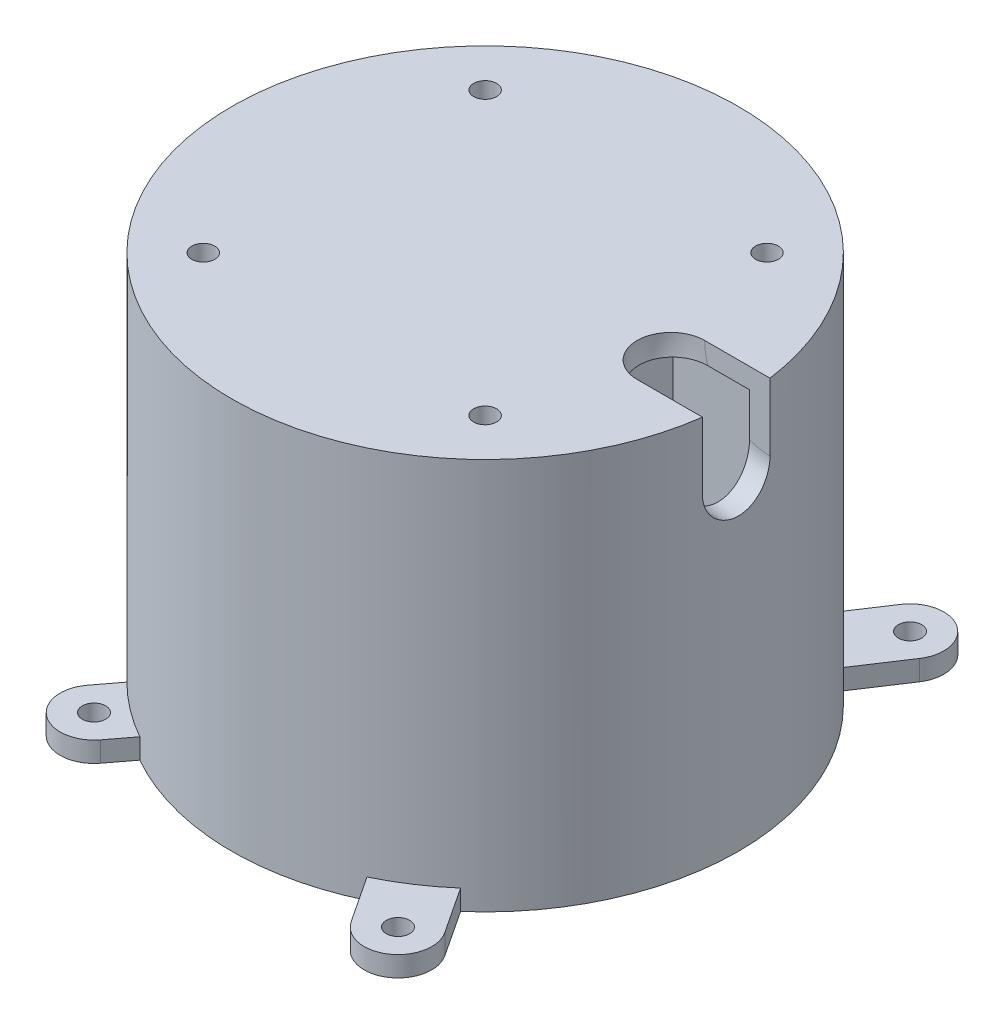
SolidWorks part; units mm, degrees
ref_plane "Front Plane" through (0, 0, 0) normal (0, 0, 1) x (1, 0, 0)
ref_plane "Top Plane" through (0, 0, 0) normal (0, 1, 0) x (1, 0, 0)
ref_plane "Right Plane" through (0, 0, 0) normal (1, 0, 0) x (0, 0, -1)
sketch "Sketch1" plane through (0, 0, 0) normal (0, 1, 0) x (1, 0, 0)
  circle A6 centre (0, 0) radius 37.5
  dimension "D1" = 75
extrude "Boss-Extrude2" add sketch "Sketch1" against normal blind 3
sketch "Sketch2" plane through (0, -3, 0) normal (0, -1, 0) x (1, 0, 0)
  line L4 (0, 32.7824) -> (0, 0) construction
  circle A0 centre (0, 0) radius 34.5
  circle A1 centre (0, 0) radius 37.5
  circle A2 centre (0, 0) radius 37.5
  point P5 (0, 34.025)
  point P7 (10.4973, 36.0008)
  point P8 (10.4066, 32.7824)
  dimension "D2" = 3
  dimension "D1" = 0
extrude "Boss-Extrude3" add sketch "Sketch2" along normal blind 55
sketch "Sketch3" plane through (0, -3, 0) normal (0, -1, 0) x (1, 0, 0)
  line L0 (13.5, 34.9857) -> (13.5, 31.749)
  line L8 (13.5, 31.749) -> (-13.5, 31.749)
  line L9 (-13.5, 31.749) -> (-13.5, 34.9857)
  line L10 (0, 0) -> (-12.0832, 0) construction
  line L11 (-13.5, -31.749) -> (-13.5, -34.9857)
  line L12 (13.5, -31.749) -> (-13.5, -31.749)
  line L13 (13.5, -34.9857) -> (13.5, -31.749)
  circle A4 centre (0, 0) radius 37.5 construction
  arc A5 (13.5, 34.9857) -> (-13.5, 34.9857) centre (0, 0) ccw
  circle A6 centre (0, 0) radius 34.5 construction
  arc A7 (13.5, -34.9857) -> (-13.5, -34.9857) centre (0, 0) cw
  dimension "D1" = 27
extrude "Boss-Extrude4" add sketch "Sketch3" along normal up to surface (55 mm away) up to face at (0, -58, -37.5)
sketch "Sketch4" plane through (0, 0, 0) normal (0, 0, 1) x (1, 0, 0)
  line L0 (-12.625, -14.83) -> (-12.625, -9.67) construction
  line L1 (12.625, -9.67) -> (12.625, -14.83) construction
  line L2 (-12.625, -14.83) -> (-12.625, -9.67) construction
  line L3 (12.625, -9.67) -> (12.625, -14.83) construction
  line L4 (-12.825, -3) -> (-12.825, -14.83)
  line L5 (-12.125, -17.0499) -> (-12.125, -19.0499)
  line L6 (-12.125, -19.0499) -> (-17.825, -19.0499)
  line L7 (-17.825, -19.0499) -> (-17.825, -3)
  line L8 (-17.825, -3) -> (-12.825, -3)
  line L10 (0, 0) -> (0, -13.0317) construction
  line L11 (17.825, -19.0499) -> (17.825, -3)
  line L12 (12.125, -19.0499) -> (17.825, -19.0499)
  line L13 (12.125, -17.0499) -> (12.125, -19.0499)
  line L14 (12.825, -3) -> (12.825, -14.83)
  line L15 (17.825, -3) -> (12.825, -3)
  line L16 (13.5, -3) -> (34.5, -3) construction
  arc A0 (-12.825, -14.83) -> (-12.125, -17.0499) centre (-8.955, -14.83) ccw
  arc A2 (12.825, -14.83) -> (12.125, -17.0499) centre (8.955, -14.83) cw
  arc A3 (-12.625, -14.83) -> (-8.955, -18.5) centre (-8.955, -14.83) ccw construction
  point P12 (0, 0)
  point P27 (-12.1309, -18.4005)
  dimension "D1" = 0.2
  dimension "D2" = 0.7
  dimension "D3" = 2
  dimension "D4" = 5
extrude "Boss-Extrude5" add sketch "Sketch4" along normal mid plane 20
ref_plane "Plane1" through (37.5, 0, 0) normal (1, 0, 0) x (0, 0, -1)
sketch "Sketch7" plane through (0, -58, 0) normal (0, -1, 0) x (1, 0, 0)
  circle A0 centre (0, 0) radius 37.5
  circle A1 centre (0, 0) radius 31.5
  circle A2 centre (0, 0) radius 37.5 construction
  dimension "D1" = 6
extrude "Boss-Extrude7" add sketch "Sketch7" against normal blind 3
hole_wizard "M3 Clearance Hole1" positions "Sketch8" profile "Sketch10" hole size "M3" standard "ANSI Metric" end condition through all
sketch "Sketch8" plane through (0, -3, 0) normal (0, -1, 0) x (-1, 0, 0)
  circle A2 centre (20.8597, -20.8597) radius 1.6
  circle A3 centre (20.8597, -20.8597) radius 1.6
  circle A6 centre (-20.8597, -20.8597) radius 1.6
  circle A7 centre (-20.8597, -20.8597) radius 1.6
  circle A10 centre (-20.8597, 20.8597) radius 1.6
  circle A11 centre (-20.8597, 20.8597) radius 1.6
  circle A14 centre (20.8597, 20.8597) radius 1.6
  circle A15 centre (20.8597, 20.8597) radius 1.6
  point P5 (20.8597, -20.8597)
  point P12 (-20.8597, -20.8597)
  point P19 (-20.8597, 20.8597)
  point P26 (20.8597, 20.8597)
  dimension "D1" = 0
  dimension "D2" = 0
  dimension "D3" = 0
  dimension "D4" = 0
sketch "Sketch10" plane through (-20.8597, -3, 20.8597) normal (1, 0, 0) x (0, 0, -1)
  line L0 (0, 0) -> (0, 3)
  line L1 (0, 3) -> (1.7, 3)
  line L2 (1.7, 3) -> (1.7, 0)
  line L5 (1.7, 0) -> (0, 0)
  line L11 (0, -6.35) -> (0, 107.95) construction
  dimension "Thru Hole Dia." = 3.4
  dimension "Thru Hole Depth" = 3
sketch "Sketch11" plane through (0, 0, 0) normal (0, 1, 0) x (1, 0, 0)
  line L0 (37.5, -5) -> (27.5, -5)
  line L1 (27.5, 5) -> (37.5, 5)
  line L2 (27.5, 0) -> (0, 0) construction
  line L3 (37.5, -5) -> (37.5, 5)
  arc A0 (27.5, -5) -> (27.5, 5) centre (27.5, 0) cw
  circle A1 centre (0, 0) radius 37.5 construction
  point P2 (22.5, 0)
  point P3 (0, 0)
  point P4 (37.5, 0)
  point P9 (36.8473, 1.8668)
  point P12 (0, 0)
  dimension "D3" = 15
  dimension "D2" = 10
revolve "Cut-Revolve1" cut sketch "Sketch11" angle 360 about L3
sketch "Sketch14" plane through (0, -58, 0) normal (0, -1, 0) x (1, 0, 0)
  line L0 (25, 37.9) -> (25, 32.9)
  line L1 (25, 32.9) -> (-25, 32.9)
  line L2 (0, -32.9) -> (0, 32.9)
  line L3 (0, 0) -> (13.3551, 0) construction
  line L4 (25, -32.9) -> (-25, -32.9)
  line L5 (25, -37.9) -> (25, -32.9)
  point P7 (0, 0)
  dimension "D1" = 50
  dimension "D2" = 5
  dimension "D3" = 65.8
sketch "Sketch15" plane through (0, -58, 0) normal (0, -1, 0) x (1, 0, 0)
  line L0 (24.6379, 28.2705) -> (29.1738, 35.1469)
  line L1 (20.8262, 40.6531) -> (16.2904, 33.7768)
  line L2 (-26.4668, 26.5661) -> (-28.981, 29.8749)
  line L3 (-21.019, 35.9251) -> (-18.5047, 32.6163)
  line L5 (-25, 32.9) -> (0, 0) construction
  line L6 (0, 0) -> (25, 37.9) construction
  line L7 (0, 0) -> (-26.4668, 0) construction
  line L8 (-21.019, -35.9251) -> (-18.5047, -32.6163)
  line L9 (-26.4668, -26.5661) -> (-28.981, -29.8749)
  line L10 (24.6379, -28.2705) -> (29.1738, -35.1469)
  line L11 (20.8262, -40.6531) -> (16.2904, -33.7768)
  circle A0 centre (0, 0) radius 37.5 construction
  arc A1 (29.1738, 35.1469) -> (20.8262, 40.6531) centre (25, 37.9) ccw
  arc A2 (-18.5047, 32.6163) -> (-26.4668, 26.5661) centre (0, 0) ccw
  arc A3 (-28.981, 29.8749) -> (-21.019, 35.9251) centre (-25, 32.9) cw
  arc A4 (24.6379, 28.2705) -> (16.2904, 33.7768) centre (0, 0) ccw
  arc A5 (-28.981, -29.8749) -> (-21.019, -35.9251) centre (-25, -32.9) ccw
  arc A6 (-18.5047, -32.6163) -> (-26.4668, -26.5661) centre (0, 0) cw
  arc A7 (29.1738, -35.1469) -> (20.8262, -40.6531) centre (25, -37.9) cw
  arc A8 (24.6379, -28.2705) -> (16.2904, -33.7768) centre (0, 0) cw
  dimension "D1" = 10
extrude "Boss-Extrude8" add sketch "Sketch15" against normal blind 3
hole_wizard "Tap Drill for #8-32 Tap1" positions "Sketch16" profile "Sketch17" hole size "#8-32" standard "ANSI Inch" end condition through all
sketch "Sketch16" plane through (0, -58, 0) normal (0, -1, 0) x (-1, 0, 0)
  point P0 (-25, -37.9)
  point P3 (25, -32.9)
  point P6 (-25, 37.9)
  point P9 (25, 32.9)
sketch "Sketch17" plane through (25, -58, 37.9) normal (1, 0, 0) x (0, 0, -1)
  line L0 (0, 0) -> (0, 58)
  line L1 (0, 58) -> (1.7272, 58)
  line L2 (1.7272, 58) -> (1.7272, 0)
  line L5 (1.7272, 0) -> (0, 0)
  line L11 (0, -6.35) -> (0, 107.95) construction
  dimension "Thru Hole Dia." = 3.4544
  dimension "Thru Hole Depth" = 58
sketch "Sketch18" plane through (0, -3, 0) normal (0, -1, 0) x (1, 0, 0)
  line L1 (-12.825, 20) -> (12.825, 20)
  line L2 (-12.825, 20) -> (-12.825, -20)
  line L3 (-12.825, -20) -> (12.825, -20)
  line L4 (12.825, 20) -> (12.825, -20)
  line L5 (-12.825, 20) -> (12.825, -20) construction
  line L6 (-12.825, -20) -> (12.825, 20) construction
  point P0 (0, 0)
  dimension "D1" = 40
extrude "Boss-Extrude9" add sketch "Sketch18" along normal blind 3
sketch "Sketch19" plane through (0, 0, -31.749) normal (0, 0, 1) x (1, 0, 0)
  line L0 (8.955, -18.5) -> (-8.955, -18.5) construction
  line L1 (10.75, -5.5) -> (-10.75, -5.5)
  line L2 (10.75, -5.5) -> (10.75, -18.5)
  line L3 (10.75, -18.5) -> (-10.75, -18.5)
  line L4 (-10.75, -5.5) -> (-10.75, -18.5)
  line L5 (0, 0) -> (0, -5.5) construction
  line L6 (-8.955, -6) -> (5.61, -6) construction
  line L7 (-8.955, -6) -> (5.61, -6) construction
  dimension "D1" = 1
  dimension "D2" = 21.5
extrude "Cut-Extrude4" cut sketch "Sketch19" against normal through all
fillet "Fillet2" radius 2 4 edges at (-10.75, -5.5, -33.8376) (10.75, -5.5, -33.8376) (10.75, -18.5, -33.8376) (-10.75, -18.5, -33.8376)
